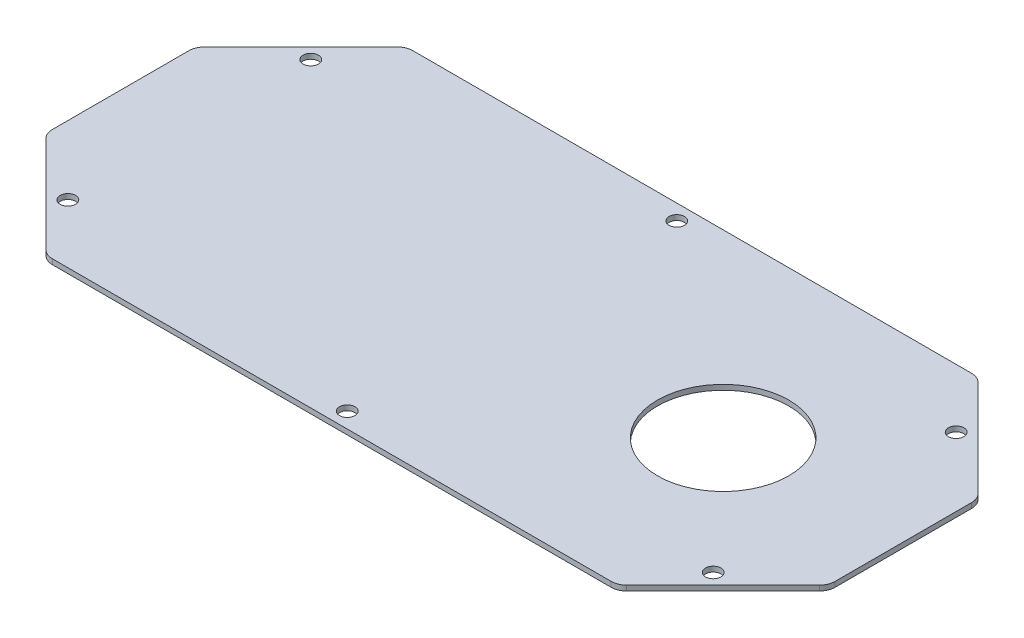
SolidWorks part; units mm, degrees
ref_plane "Спереди" through (0, 0, 0) normal (0, 0, 1) x (1, 0, 0)
ref_plane "Сверху" through (0, 0, 0) normal (0, 1, 0) x (1, 0, 0)
ref_plane "Справа" through (0, 0, 0) normal (1, 0, 0) x (0, 0, -1)
sketch "Эскиз1" plane through (0, 0, 0) normal (0, 1, 0) x (1, 0, 0)
  line L0 (35, 0) -> (-143.9615, 0) construction
  line L1 (-96.5025, -35) -> (14.4975, -35)
  line L2 (14.4975, -35) -> (35, -14.4975)
  line L3 (35, -14.4975) -> (35, 14.4975)
  line L4 (35, 14.4975) -> (14.4975, 35)
  line L5 (14.4975, 35) -> (-96.5025, 35)
  line L6 (14.4975, 35) -> (14.4975, -35) construction
  line L7 (-96.5025, 35) -> (-117.0055, 14.497)
  line L8 (-96.5025, -35) -> (-117.0055, -14.497)
  line L9 (-117.0055, 0) -> (-117.0055, 14.497)
  line L10 (-117.0055, 0) -> (-117.0055, -14.497)
  line L13 (-35, 14.4975) -> (-35, -14.4975) [skipped]
  line L14 (-14.4975, 35) -> (-35, 14.4975) [skipped]
  line L15 (-35, -14.4975) -> (-14.4975, -35) [skipped]
  circle A0 centre (0, 0) radius 35 construction
  circle A1 centre (-82.0055, 0) radius 35 construction
  dimension "D1" = 70
  dimension "D2" = 111
  dimension "D3" = 111
  dimension "D4" = 14.4975
  dimension "D5" = 14.497
sheet metal parameters "Листовой металл1" thickness 1 parameters "D1"=1.2, "Толщина"=1
base flange "Базовая кромка1" sketch "Эскиз1" thickness 1 reverse thickness direction no parameters "D1"=1.2
sketch "Эскиз2" plane through (0, 0, 0) normal (0, 1, 0) x (1, 0, 0)
  line L0 (-114.0055, -13.2544) -> (-114.0055, 13.2544) construction
  line L1 (-114.0055, 13.2544) -> (-95.2599, 32) construction
  line L2 (-95.2599, 32) -> (13.2548, 32) construction
  line L3 (13.2548, 32) -> (32, 13.2548) construction
  line L4 (32, 13.2548) -> (32, -13.2548) construction
  line L5 (32, -13.2548) -> (13.2548, -32) construction
  line L6 (13.2548, -32) -> (-95.2599, -32) construction
  line L7 (-95.2599, -32) -> (-114.0055, -13.2544) construction
  line L8 (14.4975, 35) -> (-96.5025, 35) construction
  line L9 (-96.5025, 35) -> (-117.0055, 14.497) construction
  line L10 (-117.0055, 14.497) -> (-117.0055, -14.497) construction
  line L11 (-117.0055, -14.497) -> (-96.5025, -35) construction
  line L12 (-96.5025, -35) -> (14.4975, -35) construction
  line L13 (14.4975, -35) -> (35, -14.4975) construction
  line L14 (35, -14.4975) -> (35, 14.4975) construction
  line L15 (35, 14.4975) -> (14.4975, 35) construction
  line L16 (-106.754, 24.7485) -> (24.7487, -24.7487) construction
  line L17 (24.7487, -24.7487) -> (24.7487, 24.7487) construction
  line L18 (24.7487, 24.7487) -> (-106.754, -24.7485) construction
  line L19 (-41.0025, 35) -> (-41.0025, -36.19) construction
  circle A0 centre (-103.6716, 23.5883) radius 1.5
  circle A1 centre (-41.0025, 32) radius 1.5
  circle A2 centre (21.6663, 23.5885) radius 1.5
  circle A3 centre (21.6663, -23.5885) radius 1.5
  circle A4 centre (-103.6716, -23.5883) radius 1.5
  circle A5 centre (-41.0025, -32) radius 1.5
  dimension "D9" = 3
  dimension "D10" = 3
  dimension "D11" = 3
  dimension "D12" = 3
  dimension "D13" = 3
  dimension "D14" = 3
  dimension "D1" = 3
  dimension "D2" = 3
  dimension "D3" = 3
  dimension "D4" = 3
  dimension "D5" = 3
  dimension "D6" = 3
  dimension "D7" = 3
  dimension "D8" = 3
extrude "Вырез-Вытянуть1" cut sketch "Эскиз2" against normal blind 10 normal cut yes
fillet "Скругление1" radius 3 8 edges at (35, -0.5, -14.4975) (14.4975, -0.5, -35) (-96.5025, -0.5, -35) (-117.0055, -0.5, -14.497) (-117.0055, -0.5, 14.497) (-96.5025, -0.5, 35) (35, -0.5, 14.4975) (14.4975, -0.5, 35)
sketch "Эскиз3" plane through (0, -1, 0) normal (0, -1, 0) x (1, 0, 0)
  circle A0 centre (0, 0) radius 12.75
  dimension "D1" = 25.5
extrude "Вырез-Вытянуть2" cut sketch "Эскиз3" against normal blind 10 normal cut yes
flat pattern "Развертка1" [suppressed]
sketch "Сгиб-Линии1" plane through (0, 0, 0) normal (0, 1, 0) x (1, 0, 0)
sketch3d "Граничная рамка1" [suppressed]
  line L0 (35, 35, 0) -> (35, -35, 0) construction
  line L1 (-35, 35, 0) -> (-35, -35, 0) construction
  line L2 (35, 35, 0) -> (-35, 35, 0) construction
  line L3 (35, -35, 0) -> (-35, -35, 0) construction
